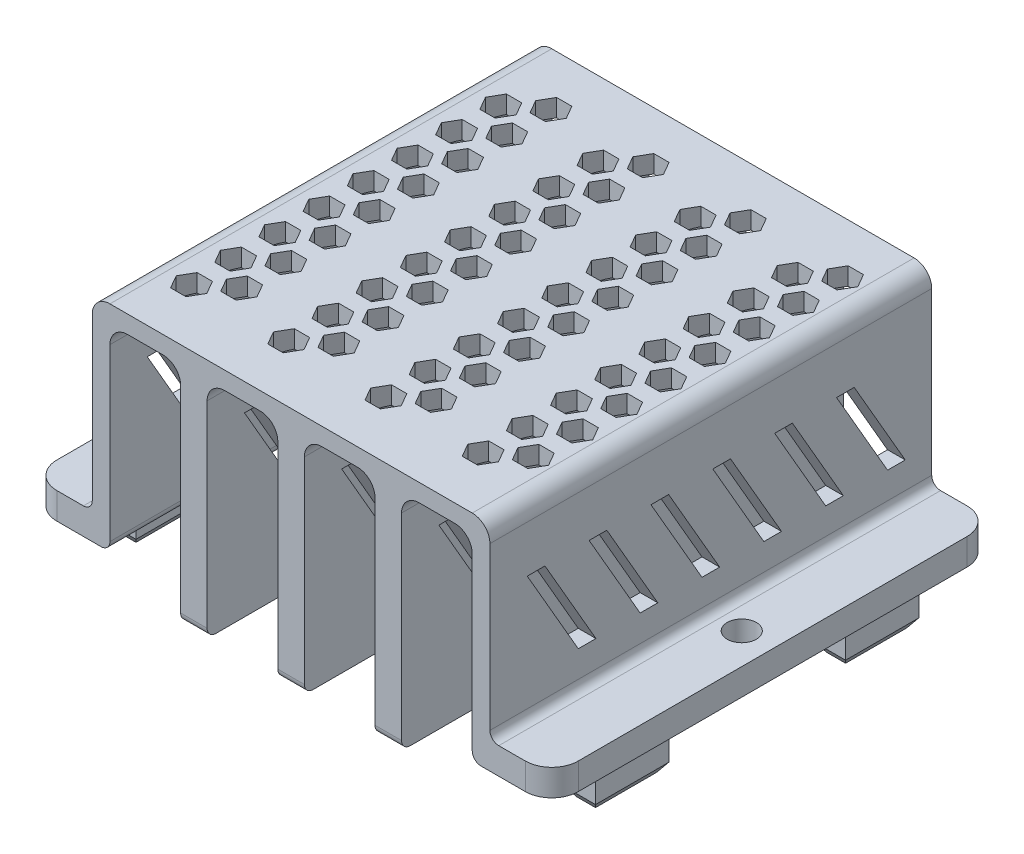
SolidWorks part; units mm, degrees
ref_plane "Front Plane" through (0, 0, 0) normal (0, 0, 1) x (1, 0, 0)
ref_plane "Top Plane" through (0, 0, 0) normal (0, 1, 0) x (1, 0, 0)
ref_plane "Right Plane" through (0, 0, 0) normal (1, 0, 0) x (0, 0, -1)
sketch "Sketch1" plane through (0, 0, 0) normal (0, 0, 1) x (1, 0, 0)
  line L0 (-29.5, -9.15) -> (-22.5, -9.15)
  line L1 (29.5, -12.15) -> (-29.5, -12.15) construction
  line L2 (29.5, -12.15) -> (29.5, 12.15) construction
  line L3 (29.5, 12.15) -> (-29.5, 12.15) construction
  line L4 (-29.5, -12.15) -> (-29.5, 12.15) construction
  line L5 (29.5, -12.15) -> (-29.5, 12.15) construction
  line L6 (29.5, 12.15) -> (-29.5, -12.15) construction
  line L7 (-22.5, -9.15) -> (-22.5, 12.15)
  line L8 (-22.5, 12.15) -> (22.5, 12.15)
  line L9 (22.5, 12.15) -> (22.5, -9.15)
  line L10 (22.5, -9.15) -> (29.5, -9.15)
  line L11 (29.5, -9.15) -> (29.5, -12.15)
  line L12 (29.5, -12.15) -> (-29.5, -12.15)
  line L13 (-29.5, -12.15) -> (-29.5, -9.15)
  point P0 (0, 0)
  point P8 (0, 12.15)
  point P13 (0, -12.15)
  dimension "D1" = 45
  dimension "D2" = 24.3
  dimension "D3" = 3
  dimension "D4" = 7
extrude "Boss-Extrude1" add sketch "Sketch1" against normal blind 50
sketch "Sketch2" plane through (0, 0, 0) normal (0, 0, 1) x (1, 0, 0)
  line L0 (-29.5, -12.15) -> (29.5, -12.15) construction
  line L1 (20.5, -12.15) -> (-20.5, -12.15)
  line L2 (20.5, -12.15) -> (20.5, 10.15)
  line L3 (20.5, 10.15) -> (-20.5, 10.15)
  line L4 (-20.5, -12.15) -> (-20.5, 10.15)
  line L5 (20.5, -12.15) -> (-20.5, 10.15) construction
  line L6 (20.5, 10.15) -> (-20.5, -12.15) construction
  line L7 (22.5, 12.15) -> (-22.5, 12.15) construction
  line L8 (22.5, -9.15) -> (22.5, 12.15) construction
  line L9 (-22.5, 12.15) -> (-22.5, -9.15) construction
  point P0 (0, -1)
  dimension "D1" = 2
  dimension "D2" = 2
  dimension "D3" = 2
extrude "Cut-Extrude1" cut sketch "Sketch2" against normal up to surface (50 mm away) up to face at (0, -4.575, -50)
sketch "Sketch3" plane through (0, -9.15, 0) normal (0, 1, 0) x (1, 0, 0)
  line L0 (-29.5, 50) -> (-29.5, 0) construction
  line L1 (-22.5, 50) -> (-29.5, 50) construction
  line L2 (29.5, 50) -> (22.5, 50) construction
  circle A0 centre (-26, 25) radius 1.65
  circle A1 centre (26, 25) radius 1.65
  point P5 (-29.5, 25)
  point P6 (-26, 50)
  point P9 (26, 50)
  dimension "D1" = 3.3
extrude "Cut-Extrude2" cut sketch "Sketch3" against normal up to surface (3 mm away) up to face at (25, -12.15, -25)
sketch "Sketch4" plane through (0, -12.15, 0) normal (0, -1, 0) x (1, 0, 0)
  line L1 (-27.75, -6.7) -> (-24.25, -6.7)
  line L2 (-27.75, -6.7) -> (-27.75, -15)
  line L3 (-27.75, -15) -> (-24.25, -15)
  line L4 (-24.25, -6.7) -> (-24.25, -15)
  line L5 (-27.75, -6.7) -> (-24.25, -15) construction
  line L6 (-27.75, -15) -> (-24.25, -6.7) construction
  line L7 (-27.75, -35) -> (-24.25, -35)
  line L8 (-27.75, -35) -> (-27.75, -43.3)
  line L9 (-27.75, -43.3) -> (-24.25, -43.3)
  line L10 (-24.25, -35) -> (-24.25, -43.3)
  line L11 (-27.75, -35) -> (-24.25, -43.3) construction
  line L12 (-27.75, -43.3) -> (-24.25, -35) construction
  line L13 (24.25, -6.7) -> (27.75, -6.7)
  line L14 (24.25, -6.7) -> (24.25, -15)
  line L15 (24.25, -15) -> (27.75, -15)
  line L16 (27.75, -6.7) -> (27.75, -15)
  line L17 (24.25, -6.7) -> (27.75, -15) construction
  line L18 (24.25, -15) -> (27.75, -6.7) construction
  line L19 (24.25, -35) -> (27.75, -35)
  line L20 (24.25, -35) -> (24.25, -43.3)
  line L21 (24.25, -43.3) -> (27.75, -43.3)
  line L22 (27.75, -35) -> (27.75, -43.3)
  line L23 (24.25, -35) -> (27.75, -43.3) construction
  line L24 (24.25, -43.3) -> (27.75, -35) construction
  point P4 (-26, -10.85)
  point P9 (-26, -39.15)
  point P14 (26, -10.85)
  point P19 (26, -39.15)
  point P20 (-26, -25)
  point P21 (26, -25)
  dimension "D1" = 3.5
  dimension "D2" = 8.3
  dimension "D3" = 10
  dimension "D4" = 10
extrude "Boss-Extrude2" add sketch "Sketch4" along normal blind 5
sketch "Sketch5" plane through (0, 0, -50) normal (0, 0, -1) x (-1, 0, 0)
  line L0 (-20.5, 10.15) -> (20.5, 10.15) construction
  line L1 (-12.5, 10.15) -> (-9.5, 10.15)
  line L2 (-12.5, 10.15) -> (-12.5, -15.15)
  line L3 (-12.5, -15.15) -> (-9.5, -15.15)
  line L4 (-9.5, 10.15) -> (-9.5, -15.15)
  line L5 (-12.5, 10.15) -> (-9.5, -15.15) construction
  line L6 (-12.5, -15.15) -> (-9.5, 10.15) construction
  line L7 (-20.5, -12.15) -> (-20.5, 10.15) construction
  line L8 (-1.5, 10.15) -> (1.5, 10.15)
  line L9 (-1.5, 10.15) -> (-1.5, -15.15)
  line L10 (-1.5, -15.15) -> (1.5, -15.15)
  line L11 (1.5, 10.15) -> (1.5, -15.15)
  line L12 (-1.5, 10.15) -> (1.5, -15.15) construction
  line L13 (-1.5, -15.15) -> (1.5, 10.15) construction
  line L14 (9.5, 10.15) -> (12.5, 10.15)
  line L15 (9.5, 10.15) -> (9.5, -15.15)
  line L16 (9.5, -15.15) -> (12.5, -15.15)
  line L17 (12.5, 10.15) -> (12.5, -15.15)
  line L18 (9.5, 10.15) -> (12.5, -15.15) construction
  line L19 (9.5, -15.15) -> (12.5, 10.15) construction
  line L21 (-20.5, -12.15) -> (-29.5, -12.15) construction
  point P4 (-11, -2.5)
  point P11 (0, -2.5)
  point P16 (11, -2.5)
  dimension "D1" = 3
  dimension "D2" = 3
  dimension "D3" = 3
  dimension "D4" = 8
  dimension "D5" = 8
  dimension "D6" = 8
  dimension "D7" = 3
extrude "Boss-Extrude3" add sketch "Sketch5" against normal up to surface (50 mm away) up to face at (0, -3.3833, 0)
sketch "Sketch6" plane through (0, 10.15, 0) normal (0, -1, 0) x (1, 0, 0)
  line L0 (-12.5, 0) -> (-20.5, 0) construction
  line L1 (-16.9019, -8) -> (-16.0359, -6.5)
  line L2 (-16.0359, -6.5) -> (-16.9019, -5)
  line L3 (-16.9019, -5) -> (-18.634, -5)
  line L4 (-18.634, -5) -> (-19.5, -6.5)
  line L5 (-19.5, -6.5) -> (-18.634, -8)
  line L6 (-18.634, -8) -> (-16.9019, -8)
  line L7 (-12.8605, -9) -> (-13.7265, -7.5)
  line L8 (-13.7265, -7.5) -> (-15.4585, -7.5)
  line L9 (-15.4585, -7.5) -> (-16.3246, -9)
  line L10 (-16.3246, -9) -> (-15.4585, -10.5)
  line L11 (-15.4585, -10.5) -> (-13.7265, -10.5)
  line L12 (-13.7265, -10.5) -> (-12.8605, -9)
  line L19 (-20.5, -50) -> (-20.5, 0) construction
  line L20 (-16.9019, -13) -> (-16.0359, -11.5)
  line L21 (-16.0359, -11.5) -> (-16.9019, -10)
  line L22 (-16.9019, -10) -> (-18.634, -10)
  line L23 (-18.634, -10) -> (-19.5, -11.5)
  line L24 (-19.5, -11.5) -> (-18.634, -13)
  line L25 (-18.634, -13) -> (-16.9019, -13)
  line L26 (-12.8605, -14) -> (-13.7265, -12.5)
  line L27 (-13.7265, -12.5) -> (-15.4585, -12.5)
  line L28 (-15.4585, -12.5) -> (-16.3246, -14)
  line L29 (-16.3246, -14) -> (-15.4585, -15.5)
  line L30 (-15.4585, -15.5) -> (-13.7265, -15.5)
  line L31 (-13.7265, -15.5) -> (-12.8605, -14)
  line L32 (-16.9019, -18) -> (-16.0359, -16.5)
  line L33 (-16.0359, -16.5) -> (-16.9019, -15)
  line L34 (-16.9019, -15) -> (-18.634, -15)
  line L35 (-18.634, -15) -> (-19.5, -16.5)
  line L36 (-19.5, -16.5) -> (-18.634, -18)
  line L37 (-18.634, -18) -> (-16.9019, -18)
  line L38 (-12.8605, -19) -> (-13.7265, -17.5)
  line L39 (-13.7265, -17.5) -> (-15.4585, -17.5)
  line L40 (-15.4585, -17.5) -> (-16.3246, -19)
  line L41 (-16.3246, -19) -> (-15.4585, -20.5)
  line L42 (-15.4585, -20.5) -> (-13.7265, -20.5)
  line L43 (-13.7265, -20.5) -> (-12.8605, -19)
  line L44 (-16.9019, -23) -> (-16.0359, -21.5)
  line L45 (-16.0359, -21.5) -> (-16.9019, -20)
  line L46 (-16.9019, -20) -> (-18.634, -20)
  line L47 (-18.634, -20) -> (-19.5, -21.5)
  line L48 (-19.5, -21.5) -> (-18.634, -23)
  line L49 (-18.634, -23) -> (-16.9019, -23)
  line L50 (-12.8605, -24) -> (-13.7265, -22.5)
  line L51 (-13.7265, -22.5) -> (-15.4585, -22.5)
  line L52 (-15.4585, -22.5) -> (-16.3246, -24)
  line L53 (-16.3246, -24) -> (-15.4585, -25.5)
  line L54 (-15.4585, -25.5) -> (-13.7265, -25.5)
  line L55 (-13.7265, -25.5) -> (-12.8605, -24)
  line L56 (-16.9019, -28) -> (-16.0359, -26.5)
  line L57 (-16.0359, -26.5) -> (-16.9019, -25)
  line L58 (-16.9019, -25) -> (-18.634, -25)
  line L59 (-18.634, -25) -> (-19.5, -26.5)
  line L60 (-19.5, -26.5) -> (-18.634, -28)
  line L61 (-18.634, -28) -> (-16.9019, -28)
  line L62 (-12.8605, -29) -> (-13.7265, -27.5)
  line L63 (-13.7265, -27.5) -> (-15.4585, -27.5)
  line L64 (-15.4585, -27.5) -> (-16.3246, -29)
  line L65 (-16.3246, -29) -> (-15.4585, -30.5)
  line L66 (-15.4585, -30.5) -> (-13.7265, -30.5)
  line L67 (-13.7265, -30.5) -> (-12.8605, -29)
  line L68 (-16.9019, -33) -> (-16.0359, -31.5)
  line L69 (-16.0359, -31.5) -> (-16.9019, -30)
  line L70 (-16.9019, -30) -> (-18.634, -30)
  line L71 (-18.634, -30) -> (-19.5, -31.5)
  line L72 (-19.5, -31.5) -> (-18.634, -33)
  line L73 (-18.634, -33) -> (-16.9019, -33)
  line L74 (-12.8605, -34) -> (-13.7265, -32.5)
  line L75 (-13.7265, -32.5) -> (-15.4585, -32.5)
  line L76 (-15.4585, -32.5) -> (-16.3246, -34)
  line L77 (-16.3246, -34) -> (-15.4585, -35.5)
  line L78 (-15.4585, -35.5) -> (-13.7265, -35.5)
  line L79 (-13.7265, -35.5) -> (-12.8605, -34)
  line L80 (-16.9019, -38) -> (-16.0359, -36.5)
  line L81 (-16.0359, -36.5) -> (-16.9019, -35)
  line L82 (-16.9019, -35) -> (-18.634, -35)
  line L83 (-18.634, -35) -> (-19.5, -36.5)
  line L84 (-19.5, -36.5) -> (-18.634, -38)
  line L85 (-18.634, -38) -> (-16.9019, -38)
  line L86 (-12.8605, -39) -> (-13.7265, -37.5)
  line L87 (-13.7265, -37.5) -> (-15.4585, -37.5)
  line L88 (-15.4585, -37.5) -> (-16.3246, -39)
  line L89 (-16.3246, -39) -> (-15.4585, -40.5)
  line L90 (-15.4585, -40.5) -> (-13.7265, -40.5)
  line L91 (-13.7265, -40.5) -> (-12.8605, -39)
  line L92 (-16.9019, -43) -> (-16.0359, -41.5)
  line L93 (-16.0359, -41.5) -> (-16.9019, -40)
  line L94 (-16.9019, -40) -> (-18.634, -40)
  line L95 (-18.634, -40) -> (-19.5, -41.5)
  line L96 (-19.5, -41.5) -> (-18.634, -43)
  line L97 (-18.634, -43) -> (-16.9019, -43)
  line L98 (-12.8605, -44) -> (-13.7265, -42.5)
  line L99 (-13.7265, -42.5) -> (-15.4585, -42.5)
  line L100 (-15.4585, -42.5) -> (-16.3246, -44)
  line L101 (-16.3246, -44) -> (-15.4585, -45.5)
  line L102 (-15.4585, -45.5) -> (-13.7265, -45.5)
  line L103 (-13.7265, -45.5) -> (-12.8605, -44)
  line L105 (-5.9019, -8) -> (-5.0359, -6.5)
  line L106 (-5.0359, -6.5) -> (-5.9019, -5)
  line L107 (-5.9019, -5) -> (-7.634, -5)
  line L108 (-7.634, -5) -> (-8.5, -6.5)
  line L109 (-8.5, -6.5) -> (-7.634, -8)
  line L110 (-7.634, -8) -> (-5.9019, -8)
  line L111 (-1.8605, -9) -> (-2.7265, -7.5)
  line L112 (-2.7265, -7.5) -> (-4.4585, -7.5)
  line L113 (-4.4585, -7.5) -> (-5.3246, -9)
  line L114 (-5.3246, -9) -> (-4.4585, -10.5)
  line L115 (-4.4585, -10.5) -> (-2.7265, -10.5)
  line L116 (-2.7265, -10.5) -> (-1.8605, -9)
  line L117 (-5.9019, -13) -> (-5.0359, -11.5)
  line L118 (-5.0359, -11.5) -> (-5.9019, -10)
  line L119 (-5.9019, -10) -> (-7.634, -10)
  line L120 (-7.634, -10) -> (-8.5, -11.5)
  line L121 (-8.5, -11.5) -> (-7.634, -13)
  line L122 (-7.634, -13) -> (-5.9019, -13)
  line L123 (-1.8605, -14) -> (-2.7265, -12.5)
  line L124 (-2.7265, -12.5) -> (-4.4585, -12.5)
  line L125 (-4.4585, -12.5) -> (-5.3246, -14)
  line L126 (-5.3246, -14) -> (-4.4585, -15.5)
  line L127 (-4.4585, -15.5) -> (-2.7265, -15.5)
  line L128 (-2.7265, -15.5) -> (-1.8605, -14)
  line L129 (-5.9019, -18) -> (-5.0359, -16.5)
  line L130 (-5.0359, -16.5) -> (-5.9019, -15)
  line L131 (-5.9019, -15) -> (-7.634, -15)
  line L132 (-7.634, -15) -> (-8.5, -16.5)
  line L133 (-8.5, -16.5) -> (-7.634, -18)
  line L134 (-7.634, -18) -> (-5.9019, -18)
  line L135 (-1.8605, -19) -> (-2.7265, -17.5)
  line L136 (-2.7265, -17.5) -> (-4.4585, -17.5)
  line L137 (-4.4585, -17.5) -> (-5.3246, -19)
  line L138 (-5.3246, -19) -> (-4.4585, -20.5)
  line L139 (-4.4585, -20.5) -> (-2.7265, -20.5)
  line L140 (-2.7265, -20.5) -> (-1.8605, -19)
  line L141 (-5.9019, -23) -> (-5.0359, -21.5)
  line L142 (-5.0359, -21.5) -> (-5.9019, -20)
  line L143 (-5.9019, -20) -> (-7.634, -20)
  line L144 (-7.634, -20) -> (-8.5, -21.5)
  line L145 (-8.5, -21.5) -> (-7.634, -23)
  line L146 (-7.634, -23) -> (-5.9019, -23)
  line L147 (-1.8605, -24) -> (-2.7265, -22.5)
  line L148 (-2.7265, -22.5) -> (-4.4585, -22.5)
  line L149 (-4.4585, -22.5) -> (-5.3246, -24)
  line L150 (-5.3246, -24) -> (-4.4585, -25.5)
  line L151 (-4.4585, -25.5) -> (-2.7265, -25.5)
  line L152 (-2.7265, -25.5) -> (-1.8605, -24)
  line L153 (-5.9019, -28) -> (-5.0359, -26.5)
  line L154 (-5.0359, -26.5) -> (-5.9019, -25)
  line L155 (-5.9019, -25) -> (-7.634, -25)
  line L156 (-7.634, -25) -> (-8.5, -26.5)
  line L157 (-8.5, -26.5) -> (-7.634, -28)
  line L158 (-7.634, -28) -> (-5.9019, -28)
  line L159 (-1.8605, -29) -> (-2.7265, -27.5)
  line L160 (-2.7265, -27.5) -> (-4.4585, -27.5)
  line L161 (-4.4585, -27.5) -> (-5.3246, -29)
  line L162 (-5.3246, -29) -> (-4.4585, -30.5)
  line L163 (-4.4585, -30.5) -> (-2.7265, -30.5)
  line L164 (-2.7265, -30.5) -> (-1.8605, -29)
  line L165 (-5.9019, -33) -> (-5.0359, -31.5)
  line L166 (-5.0359, -31.5) -> (-5.9019, -30)
  line L167 (-5.9019, -30) -> (-7.634, -30)
  line L168 (-7.634, -30) -> (-8.5, -31.5)
  line L169 (-8.5, -31.5) -> (-7.634, -33)
  line L170 (-7.634, -33) -> (-5.9019, -33)
  line L171 (-1.8605, -34) -> (-2.7265, -32.5)
  line L172 (-2.7265, -32.5) -> (-4.4585, -32.5)
  line L173 (-4.4585, -32.5) -> (-5.3246, -34)
  line L174 (-5.3246, -34) -> (-4.4585, -35.5)
  line L175 (-4.4585, -35.5) -> (-2.7265, -35.5)
  line L176 (-2.7265, -35.5) -> (-1.8605, -34)
  line L177 (-5.9019, -38) -> (-5.0359, -36.5)
  line L178 (-5.0359, -36.5) -> (-5.9019, -35)
  line L179 (-5.9019, -35) -> (-7.634, -35)
  line L180 (-7.634, -35) -> (-8.5, -36.5)
  line L181 (-8.5, -36.5) -> (-7.634, -38)
  line L182 (-7.634, -38) -> (-5.9019, -38)
  line L183 (-1.8605, -39) -> (-2.7265, -37.5)
  line L184 (-2.7265, -37.5) -> (-4.4585, -37.5)
  line L185 (-4.4585, -37.5) -> (-5.3246, -39)
  line L186 (-5.3246, -39) -> (-4.4585, -40.5)
  line L187 (-4.4585, -40.5) -> (-2.7265, -40.5)
  line L188 (-2.7265, -40.5) -> (-1.8605, -39)
  line L189 (-5.9019, -43) -> (-5.0359, -41.5)
  line L190 (-5.0359, -41.5) -> (-5.9019, -40)
  line L191 (-5.9019, -40) -> (-7.634, -40)
  line L192 (-7.634, -40) -> (-8.5, -41.5)
  line L193 (-8.5, -41.5) -> (-7.634, -43)
  line L194 (-7.634, -43) -> (-5.9019, -43)
  line L195 (-1.8605, -44) -> (-2.7265, -42.5)
  line L196 (-2.7265, -42.5) -> (-4.4585, -42.5)
  line L197 (-4.4585, -42.5) -> (-5.3246, -44)
  line L198 (-5.3246, -44) -> (-4.4585, -45.5)
  line L199 (-4.4585, -45.5) -> (-2.7265, -45.5)
  line L200 (-2.7265, -45.5) -> (-1.8605, -44)
  line L201 (5.0981, -8) -> (5.9641, -6.5)
  line L202 (5.9641, -6.5) -> (5.0981, -5)
  line L203 (5.0981, -5) -> (3.366, -5)
  line L204 (3.366, -5) -> (2.5, -6.5)
  line L205 (2.5, -6.5) -> (3.366, -8)
  line L206 (3.366, -8) -> (5.0981, -8)
  line L207 (9.1395, -9) -> (8.2735, -7.5)
  line L208 (8.2735, -7.5) -> (6.5415, -7.5)
  line L209 (6.5415, -7.5) -> (5.6754, -9)
  line L210 (5.6754, -9) -> (6.5415, -10.5)
  line L211 (6.5415, -10.5) -> (8.2735, -10.5)
  line L212 (8.2735, -10.5) -> (9.1395, -9)
  line L213 (5.0981, -13) -> (5.9641, -11.5)
  line L214 (5.9641, -11.5) -> (5.0981, -10)
  line L215 (5.0981, -10) -> (3.366, -10)
  line L216 (3.366, -10) -> (2.5, -11.5)
  line L217 (2.5, -11.5) -> (3.366, -13)
  line L218 (3.366, -13) -> (5.0981, -13)
  line L219 (9.1395, -14) -> (8.2735, -12.5)
  line L220 (8.2735, -12.5) -> (6.5415, -12.5)
  line L221 (6.5415, -12.5) -> (5.6754, -14)
  line L222 (5.6754, -14) -> (6.5415, -15.5)
  line L223 (6.5415, -15.5) -> (8.2735, -15.5)
  line L224 (8.2735, -15.5) -> (9.1395, -14)
  line L225 (5.0981, -18) -> (5.9641, -16.5)
  line L226 (5.9641, -16.5) -> (5.0981, -15)
  line L227 (5.0981, -15) -> (3.366, -15)
  line L228 (3.366, -15) -> (2.5, -16.5)
  line L229 (2.5, -16.5) -> (3.366, -18)
  line L230 (3.366, -18) -> (5.0981, -18)
  line L231 (9.1395, -19) -> (8.2735, -17.5)
  line L232 (8.2735, -17.5) -> (6.5415, -17.5)
  line L233 (6.5415, -17.5) -> (5.6754, -19)
  line L234 (5.6754, -19) -> (6.5415, -20.5)
  line L235 (6.5415, -20.5) -> (8.2735, -20.5)
  line L236 (8.2735, -20.5) -> (9.1395, -19)
  line L237 (5.0981, -23) -> (5.9641, -21.5)
  line L238 (5.9641, -21.5) -> (5.0981, -20)
  line L239 (5.0981, -20) -> (3.366, -20)
  line L240 (3.366, -20) -> (2.5, -21.5)
  line L241 (2.5, -21.5) -> (3.366, -23)
  line L242 (3.366, -23) -> (5.0981, -23)
  line L243 (9.1395, -24) -> (8.2735, -22.5)
  line L244 (8.2735, -22.5) -> (6.5415, -22.5)
  line L245 (6.5415, -22.5) -> (5.6754, -24)
  line L246 (5.6754, -24) -> (6.5415, -25.5)
  line L247 (6.5415, -25.5) -> (8.2735, -25.5)
  line L248 (8.2735, -25.5) -> (9.1395, -24)
  line L249 (5.0981, -28) -> (5.9641, -26.5)
  line L250 (5.9641, -26.5) -> (5.0981, -25)
  line L251 (5.0981, -25) -> (3.366, -25)
  line L252 (3.366, -25) -> (2.5, -26.5)
  line L253 (2.5, -26.5) -> (3.366, -28)
  line L254 (3.366, -28) -> (5.0981, -28)
  line L255 (9.1395, -29) -> (8.2735, -27.5)
  line L256 (8.2735, -27.5) -> (6.5415, -27.5)
  line L257 (6.5415, -27.5) -> (5.6754, -29)
  line L258 (5.6754, -29) -> (6.5415, -30.5)
  line L259 (6.5415, -30.5) -> (8.2735, -30.5)
  line L260 (8.2735, -30.5) -> (9.1395, -29)
  line L261 (5.0981, -33) -> (5.9641, -31.5)
  line L262 (5.9641, -31.5) -> (5.0981, -30)
  line L263 (5.0981, -30) -> (3.366, -30)
  line L264 (3.366, -30) -> (2.5, -31.5)
  line L265 (2.5, -31.5) -> (3.366, -33)
  line L266 (3.366, -33) -> (5.0981, -33)
  line L267 (9.1395, -34) -> (8.2735, -32.5)
  line L268 (8.2735, -32.5) -> (6.5415, -32.5)
  line L269 (6.5415, -32.5) -> (5.6754, -34)
  line L270 (5.6754, -34) -> (6.5415, -35.5)
  line L271 (6.5415, -35.5) -> (8.2735, -35.5)
  line L272 (8.2735, -35.5) -> (9.1395, -34)
  line L273 (5.0981, -38) -> (5.9641, -36.5)
  line L274 (5.9641, -36.5) -> (5.0981, -35)
  line L275 (5.0981, -35) -> (3.366, -35)
  line L276 (3.366, -35) -> (2.5, -36.5)
  line L277 (2.5, -36.5) -> (3.366, -38)
  line L278 (3.366, -38) -> (5.0981, -38)
  line L279 (9.1395, -39) -> (8.2735, -37.5)
  line L280 (8.2735, -37.5) -> (6.5415, -37.5)
  line L281 (6.5415, -37.5) -> (5.6754, -39)
  line L282 (5.6754, -39) -> (6.5415, -40.5)
  line L283 (6.5415, -40.5) -> (8.2735, -40.5)
  line L284 (8.2735, -40.5) -> (9.1395, -39)
  line L285 (5.0981, -43) -> (5.9641, -41.5)
  line L286 (5.9641, -41.5) -> (5.0981, -40)
  line L287 (5.0981, -40) -> (3.366, -40)
  line L288 (3.366, -40) -> (2.5, -41.5)
  line L289 (2.5, -41.5) -> (3.366, -43)
  line L290 (3.366, -43) -> (5.0981, -43)
  line L291 (9.1395, -44) -> (8.2735, -42.5)
  line L292 (8.2735, -42.5) -> (6.5415, -42.5)
  line L293 (6.5415, -42.5) -> (5.6754, -44)
  line L294 (5.6754, -44) -> (6.5415, -45.5)
  line L295 (6.5415, -45.5) -> (8.2735, -45.5)
  line L296 (8.2735, -45.5) -> (9.1395, -44)
  line L297 (16.0981, -8) -> (16.9641, -6.5)
  line L298 (16.9641, -6.5) -> (16.0981, -5)
  line L299 (16.0981, -5) -> (14.366, -5)
  line L300 (14.366, -5) -> (13.5, -6.5)
  line L301 (13.5, -6.5) -> (14.366, -8)
  line L302 (14.366, -8) -> (16.0981, -8)
  line L303 (20.1395, -9) -> (19.2735, -7.5)
  line L304 (19.2735, -7.5) -> (17.5415, -7.5)
  line L305 (17.5415, -7.5) -> (16.6754, -9)
  line L306 (16.6754, -9) -> (17.5415, -10.5)
  line L307 (17.5415, -10.5) -> (19.2735, -10.5)
  line L308 (19.2735, -10.5) -> (20.1395, -9)
  line L309 (16.0981, -13) -> (16.9641, -11.5)
  line L310 (16.9641, -11.5) -> (16.0981, -10)
  line L311 (16.0981, -10) -> (14.366, -10)
  line L312 (14.366, -10) -> (13.5, -11.5)
  line L313 (13.5, -11.5) -> (14.366, -13)
  line L314 (14.366, -13) -> (16.0981, -13)
  line L315 (20.1395, -14) -> (19.2735, -12.5)
  line L316 (19.2735, -12.5) -> (17.5415, -12.5)
  line L317 (17.5415, -12.5) -> (16.6754, -14)
  line L318 (16.6754, -14) -> (17.5415, -15.5)
  line L319 (17.5415, -15.5) -> (19.2735, -15.5)
  line L320 (19.2735, -15.5) -> (20.1395, -14)
  line L321 (16.0981, -18) -> (16.9641, -16.5)
  line L322 (16.9641, -16.5) -> (16.0981, -15)
  line L323 (16.0981, -15) -> (14.366, -15)
  line L324 (14.366, -15) -> (13.5, -16.5)
  line L325 (13.5, -16.5) -> (14.366, -18)
  line L326 (14.366, -18) -> (16.0981, -18)
  line L327 (20.1395, -19) -> (19.2735, -17.5)
  line L328 (19.2735, -17.5) -> (17.5415, -17.5)
  line L329 (17.5415, -17.5) -> (16.6754, -19)
  line L330 (16.6754, -19) -> (17.5415, -20.5)
  line L331 (17.5415, -20.5) -> (19.2735, -20.5)
  line L332 (19.2735, -20.5) -> (20.1395, -19)
  line L333 (16.0981, -23) -> (16.9641, -21.5)
  line L334 (16.9641, -21.5) -> (16.0981, -20)
  line L335 (16.0981, -20) -> (14.366, -20)
  line L336 (14.366, -20) -> (13.5, -21.5)
  line L337 (13.5, -21.5) -> (14.366, -23)
  line L338 (14.366, -23) -> (16.0981, -23)
  line L339 (20.1395, -24) -> (19.2735, -22.5)
  line L340 (19.2735, -22.5) -> (17.5415, -22.5)
  line L341 (17.5415, -22.5) -> (16.6754, -24)
  line L342 (16.6754, -24) -> (17.5415, -25.5)
  line L343 (17.5415, -25.5) -> (19.2735, -25.5)
  line L344 (19.2735, -25.5) -> (20.1395, -24)
  line L345 (16.0981, -28) -> (16.9641, -26.5)
  line L346 (16.9641, -26.5) -> (16.0981, -25)
  line L347 (16.0981, -25) -> (14.366, -25)
  line L348 (14.366, -25) -> (13.5, -26.5)
  line L349 (13.5, -26.5) -> (14.366, -28)
  line L350 (14.366, -28) -> (16.0981, -28)
  line L351 (20.1395, -29) -> (19.2735, -27.5)
  line L352 (19.2735, -27.5) -> (17.5415, -27.5)
  line L353 (17.5415, -27.5) -> (16.6754, -29)
  line L354 (16.6754, -29) -> (17.5415, -30.5)
  line L355 (17.5415, -30.5) -> (19.2735, -30.5)
  line L356 (19.2735, -30.5) -> (20.1395, -29)
  line L357 (16.0981, -33) -> (16.9641, -31.5)
  line L358 (16.9641, -31.5) -> (16.0981, -30)
  line L359 (16.0981, -30) -> (14.366, -30)
  line L360 (14.366, -30) -> (13.5, -31.5)
  line L361 (13.5, -31.5) -> (14.366, -33)
  line L362 (14.366, -33) -> (16.0981, -33)
  line L363 (20.1395, -34) -> (19.2735, -32.5)
  line L364 (19.2735, -32.5) -> (17.5415, -32.5)
  line L365 (17.5415, -32.5) -> (16.6754, -34)
  line L366 (16.6754, -34) -> (17.5415, -35.5)
  line L367 (17.5415, -35.5) -> (19.2735, -35.5)
  line L368 (19.2735, -35.5) -> (20.1395, -34)
  line L369 (16.0981, -38) -> (16.9641, -36.5)
  line L370 (16.9641, -36.5) -> (16.0981, -35)
  line L371 (16.0981, -35) -> (14.366, -35)
  line L372 (14.366, -35) -> (13.5, -36.5)
  line L373 (13.5, -36.5) -> (14.366, -38)
  line L374 (14.366, -38) -> (16.0981, -38)
  line L375 (20.1395, -39) -> (19.2735, -37.5)
  line L376 (19.2735, -37.5) -> (17.5415, -37.5)
  line L377 (17.5415, -37.5) -> (16.6754, -39)
  line L378 (16.6754, -39) -> (17.5415, -40.5)
  line L379 (17.5415, -40.5) -> (19.2735, -40.5)
  line L380 (19.2735, -40.5) -> (20.1395, -39)
  line L381 (16.0981, -43) -> (16.9641, -41.5)
  line L382 (16.9641, -41.5) -> (16.0981, -40)
  line L383 (16.0981, -40) -> (14.366, -40)
  line L384 (14.366, -40) -> (13.5, -41.5)
  line L385 (13.5, -41.5) -> (14.366, -43)
  line L386 (14.366, -43) -> (16.0981, -43)
  line L387 (20.1395, -44) -> (19.2735, -42.5)
  line L388 (19.2735, -42.5) -> (17.5415, -42.5)
  line L389 (17.5415, -42.5) -> (16.6754, -44)
  line L390 (16.6754, -44) -> (17.5415, -45.5)
  line L391 (17.5415, -45.5) -> (19.2735, -45.5)
  line L392 (19.2735, -45.5) -> (20.1395, -44)
  line L393 (-9.5, 0) -> (-9.5, -50) construction
  circle A0 centre (-17.7679, -6.5) radius 1.5 construction
  circle A1 centre (-14.5925, -9) radius 1.5 construction
  circle A2 centre (-6.7679, -6.5) radius 1.5 construction
  circle A3 centre (-3.5925, -9) radius 1.5 construction
  circle A4 centre (4.2321, -6.5) radius 1.5 construction
  circle A5 centre (7.4075, -9) radius 1.5 construction
  circle A6 centre (15.2321, -6.5) radius 1.5 construction
  circle A7 centre (18.4075, -9) radius 1.5 construction
  dimension "D1" = 3
  dimension "D2" = 5
  dimension "D3" = 1
  dimension "D4" = 1
  dimension "D5" = 1
  dimension "D7" = 1
  dimension "D8" = 4
  dimension "D9" = 1
  dimension "D6" = 8
extrude "Cut-Extrude3" cut sketch "Sketch6" against normal up to surface (2 mm away) up to face at (0, 12.15, -25)
chamfer "Chamfer1" distance 1 angle 35 16 edges at (26, -17.15, -35) (27.75, -17.15, -39.15) (26, -17.15, -43.3) (24.25, -17.15, -39.15) (26, -17.15, -6.7) (27.75, -17.15, -10.85) (26, -17.15, -15) (24.25, -17.15, -10.85) (-26, -17.15, -35) (-24.25, -17.15, -39.15) (-26, -17.15, -43.3) (-27.75, -17.15, -39.15) (-26, -17.15, -6.7) (-24.25, -17.15, -10.85) (-26, -17.15, -15) (-27.75, -17.15, -10.85) first distance on face at (26, -14.65, -35) first distance on face at (27.75, -14.65, -39.15) first distance on face at (26, -14.65, -43.3) first distance on face at (24.25, -14.65, -39.15) first distance on face at (26, -14.65, -6.7) first distance on face at (27.75, -14.65, -10.85) first distance on face at (26, -14.65, -15) first distance on face at (24.25, -14.65, -10.85) first distance on face at (-26, -14.65, -35) first distance on face at (-24.25, -14.65, -39.15) first distance on face at (-26, -14.65, -43.3) first distance on face at (-27.75, -14.65, -39.15) first distance on face at (-26, -14.65, -6.7) first distance on face at (-24.25, -14.65, -10.85) first distance on face at (-26, -14.65, -15) first distance on face at (-27.75, -14.65, -10.85)
fillet "Fillet1" radius 1 4 edges at (-22.5, -9.15, -25) (22.5, -9.15, -25) (20.5, -12.15, -25) (-20.5, -12.15, -25)
fillet "Fillet3" radius 2 8 edges at (20.5, 10.15, -25) (12.5, 10.15, -25) (9.5, 10.15, -25) (1.5, 10.15, -25) (-1.5, 10.15, -25) (-9.5, 10.15, -25) (-12.5, 10.15, -25) (-20.5, 10.15, -25)
fillet "Fillet4" radius 0.5 16 edges at (-26, -12.15, -35) (-24.25, -12.15, -39.15) (-27.75, -12.15, -39.15) (-26, -12.15, -43.3) (-27.75, -12.15, -10.85) (-26, -12.15, -15) (-24.25, -12.15, -10.85) (-26, -12.15, -6.7) (26, -12.15, -35) (27.75, -12.15, -39.15) (24.25, -12.15, -39.15) (26, -12.15, -43.3) (24.25, -12.15, -10.85) (26, -12.15, -15) (27.75, -12.15, -10.85) (26, -12.15, -6.7)
fillet "Fillet5" radius 3 4 edges at (29.5, -10.65, -50) (29.5, -10.65, 0) (-29.5, -10.65, 0) (-29.5, -10.65, -50)
fillet "Fillet6" radius 2 2 edges at (-22.5, 12.15, -25) (22.5, 12.15, -25)
sketch "Sketch10" plane through (-22.5, 0, 0) normal (-1, 0, 0) x (0, 0, 1)
  line L0 (-41.2265, 4.85) -> (-39.2265, 4.85)
  line L1 (-41.2265, 4.85) -> (-47, -5.15)
  line L2 (-39.2265, 4.85) -> (-45, -5.15)
  line L3 (-47, -5.15) -> (-45, -5.15)
  line L4 (-50, 10.15) -> (-50, -8.15) construction
  line L5 (-50, -8.15) -> (0, -8.15) construction
  line L6 (-34.2265, 4.85) -> (-32.2265, 4.85)
  line L7 (-34.2265, 4.85) -> (-40, -5.15)
  line L8 (-40, -5.15) -> (-38, -5.15)
  line L9 (-32.2265, 4.85) -> (-38, -5.15)
  line L10 (-27.2265, 4.85) -> (-25.2265, 4.85)
  line L11 (-27.2265, 4.85) -> (-33, -5.15)
  line L12 (-33, -5.15) -> (-31, -5.15)
  line L13 (-25.2265, 4.85) -> (-31, -5.15)
  line L14 (-20.2265, 4.85) -> (-18.2265, 4.85)
  line L15 (-20.2265, 4.85) -> (-26, -5.15)
  line L16 (-26, -5.15) -> (-24, -5.15)
  line L17 (-18.2265, 4.85) -> (-24, -5.15)
  line L18 (-13.2265, 4.85) -> (-11.2265, 4.85)
  line L19 (-13.2265, 4.85) -> (-19, -5.15)
  line L20 (-19, -5.15) -> (-17, -5.15)
  line L21 (-11.2265, 4.85) -> (-17, -5.15)
  line L22 (-6.2265, 4.85) -> (-4.2265, 4.85)
  line L23 (-6.2265, 4.85) -> (-12, -5.15)
  line L24 (-12, -5.15) -> (-10, -5.15)
  line L25 (-4.2265, 4.85) -> (-10, -5.15)
  dimension "D1" = 2
  dimension "D2" = 10
  dimension "D3" = 60
  dimension "D4" = 3
  dimension "D5" = 3
  dimension "D7" = 5
  dimension "D6" = 6
extrude "Cut-Extrude7" cut sketch "Sketch10" against normal up to surface (45 mm away) up to face at (22.5, 1, -25)
fillet "Fillet7" radius 1 6 edges at (11, -15.15, 0) (0, -15.15, 0) (11, -15.15, -50) (0, -15.15, -50) (-11, -15.15, -50) (-11, -15.15, 0)
